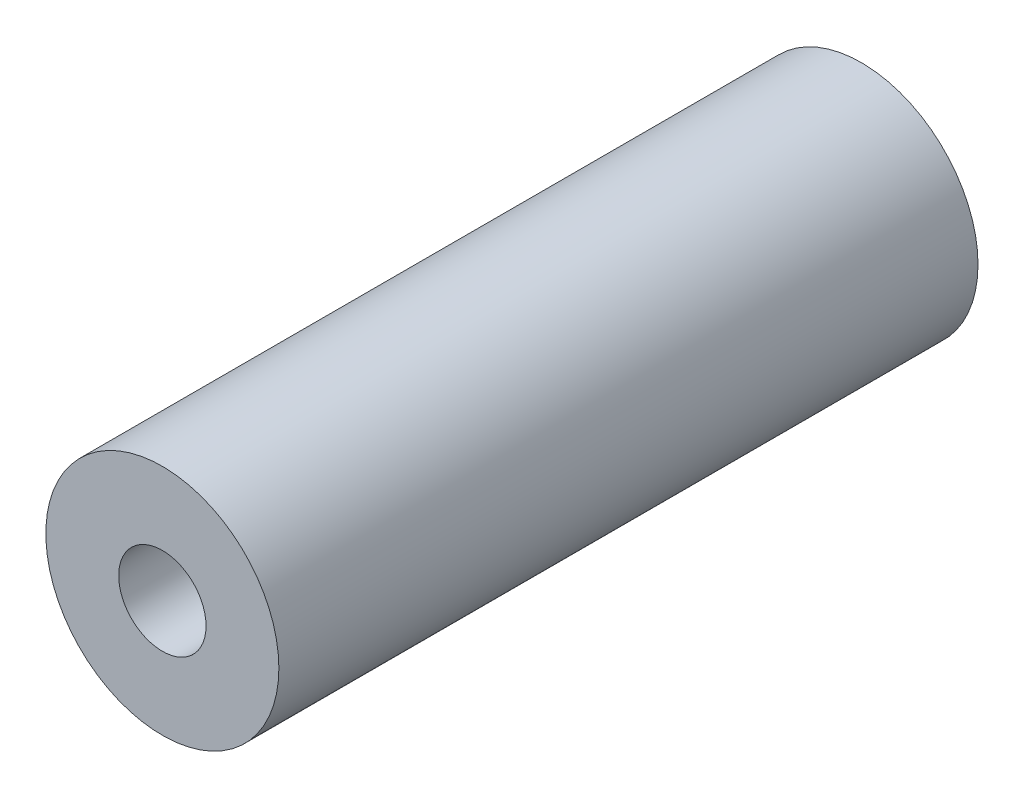
SolidWorks part; units mm, degrees
ref_plane "Front Plane" through (0, 0, 0) normal (0, 0, 1) x (1, 0, 0)
ref_plane "Top Plane" through (0, 0, 0) normal (0, 1, 0) x (1, 0, 0)
ref_plane "Right Plane" through (0, 0, 0) normal (1, 0, 0) x (0, 0, -1)
sketch "Sketch2" plane through (0, 0, 0) normal (0, 0, 1) x (1, 0, 0)
  circle A0 centre (0, 0) radius 0.75
  circle A1 centre (0, 0) radius 2
  dimension "D1" = 4
  dimension "D2" = 1.5
extrude "Boss-Extrude1" add sketch "Sketch2" along normal blind 12
